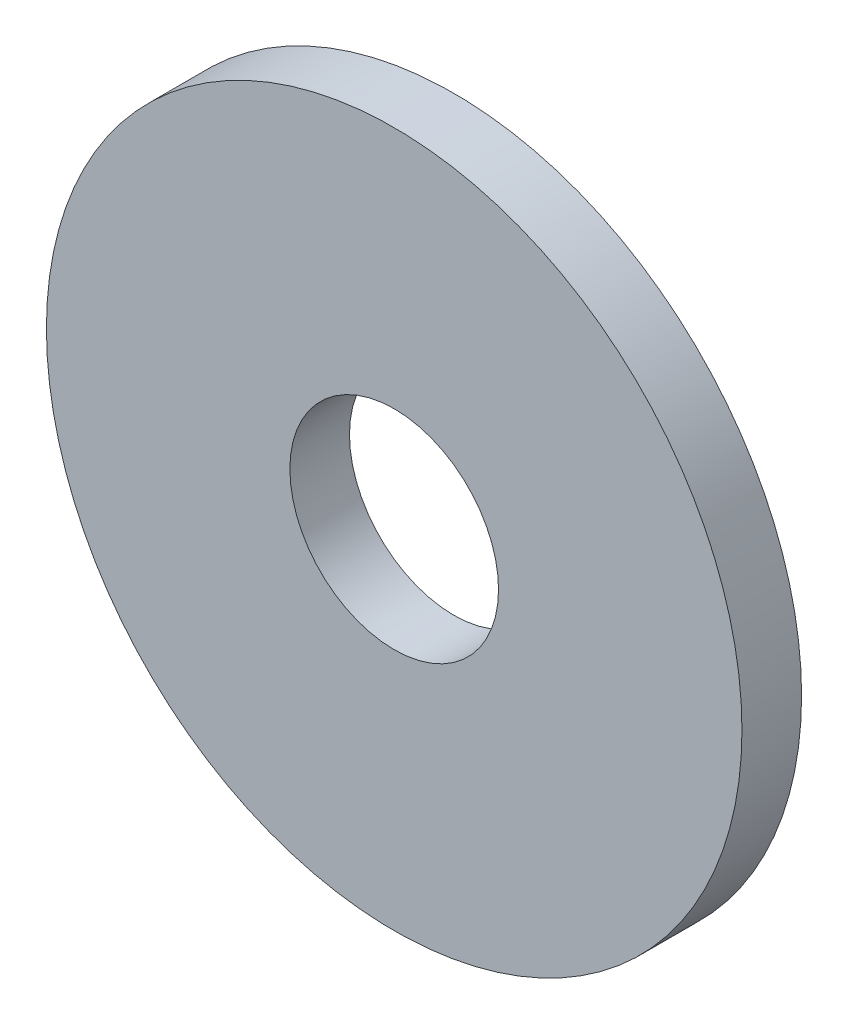
SolidWorks part; units mm, degrees
material "AISI 1020"
ref_plane "Спереди" through (0, 0, 0) normal (0, 0, 1) x (1, 0, 0)
ref_plane "Сверху" through (0, 0, 0) normal (0, 1, 0) x (1, 0, 0)
ref_plane "Справа" through (0, 0, 0) normal (1, 0, 0) x (0, 0, -1)
sketch "Эскиз1" plane through (0, 0, 0) normal (0, 0, 1) x (1, 0, 0)
  circle A0 centre (0, -155.8076) radius 17.5 construction
  circle A1 centre (0, -155.8076) radius 17.5
  circle A2 centre (0, -155.8076) radius 5.25
  dimension "D1" = 10.5
base flange "Базовая кромка1" sketch "Эскиз1" thickness 3 reverse thickness direction yes parameters "D1"=0.75
sketch "Сгиб-Линии1" [suppressed] plane through (0, 0, 0) normal (0, 1, 0) x (1, 0, 0)
sketch "Граничная рамка1" [suppressed] plane through (0, 0, 0) normal (0, 1, 0) x (1, 0, 0)
sheet metal parameters "Листовой металл3" thickness 3 parameters "D1"=0.75
flat pattern "Развертка3" [suppressed]
sketch "Сгиб-Линии2" plane through (0, 0, 0) normal (0, 1, 0) x (1, 0, 0)
sketch3d "Граничная рамка2" [suppressed]
  line L0 (17.4387, -17.561, 0) -> (-17.561, -17.4388, 0) construction
  line L1 (17.561, 17.4387, 0) -> (-17.4387, 17.5609, 0) construction
  line L2 (17.4387, -17.561, 0) -> (17.561, 17.4387, 0) construction
  line L3 (-17.561, -17.4388, 0) -> (-17.4387, 17.5609, 0) construction
